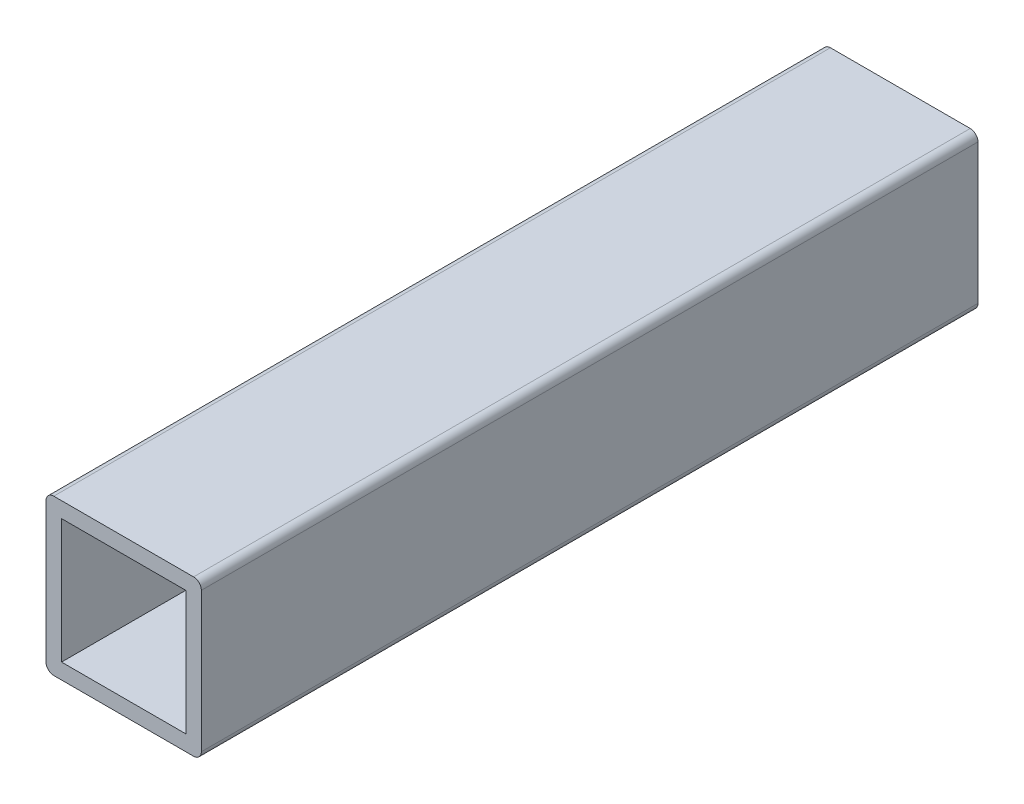
SolidWorks part; units mm, degrees
ref_plane "Front Plane" through (0, 0, 0) normal (0, 0, 1) x (1, 0, 0)
ref_plane "Top Plane" through (0, 0, 0) normal (0, 1, 0) x (1, 0, 0)
ref_plane "Right Plane" through (0, 0, 0) normal (1, 0, 0) x (0, 0, -1)
sketch "Sketch1" plane through (0, 0, 0) normal (0, 0, 1) x (1, 0, 0)
  line L0 (-12.7, -12.7) -> (-12.7, 12.7)
  line L1 (-15.875, -15.875) -> (15.875, -15.875)
  line L2 (-15.875, -15.875) -> (-15.875, 15.875)
  line L3 (-15.875, 15.875) -> (15.875, 15.875)
  line L4 (15.875, -15.875) -> (15.875, 15.875)
  line L5 (-15.875, -15.875) -> (15.875, 15.875) construction
  line L6 (-15.875, 15.875) -> (15.875, -15.875) construction
  line L7 (-12.7, 12.7) -> (12.7, 12.7)
  line L8 (12.7, -12.7) -> (12.7, 12.7)
  line L9 (-12.7, -12.7) -> (12.7, -12.7)
  point P0 (0, 0)
  point P10 (-12.7, -15.875)
  dimension "Outside Width" = 31.75
  dimension "Outside Height" = 31.75
  dimension "Wall Thickness" = 3.175
sketch "Sketch2" plane through (0, 0, 0) normal (1, 0, 0) x (0, 0, -1)
  line L0 (-914.4, 15.875) -> (914.4, 15.875) construction
  point P2 (0, 15.875)
  point P3 (-882.65, 15.875)
  point P5 (882.65, 15.875)
  dimension "Length" = 1828.8
  dimension "D1" = 31.75
  dimension "D2" = 31.75
extrude "Boss-Extrude1" add sketch "Sketch1" along normal up to vertex (914.4 mm away) and the other way up to vertex (914.4 mm away) up to point (0, 15.875, 914.4) other way up to point (0, 15.875, -914.4)
fillet "Fillet1" radius 1.5875 4 edges at (15.875, 15.875, 0) (-15.875, 15.875, 0) (-15.875, -15.875, 0) (15.875, -15.875, 0)
ref_axis "Center Axis 1" through (0, 0, -1005.84) along (0, 0, 1)
sketch "Sketch5" plane through (0, 0, 914.4) normal (0, 0, 1) x (1, 0, 0)
  line L0 (-14.2875, 15.875) -> (14.2875, 15.875)
  line L1 (-12.7, 12.7) -> (12.7, 12.7)
  line L2 (-12.7, 12.7) -> (-12.7, -12.7)
  line L3 (-12.7, -12.7) -> (12.7, -12.7)
  line L4 (12.7, 12.7) -> (12.7, -12.7)
  line L5 (-15.875, 14.2875) -> (-15.875, -14.2875)
  line L6 (15.875, 14.2875) -> (15.875, -14.2875)
  line L7 (-14.2875, -15.875) -> (14.2875, -15.875)
  arc A0 (15.875, -14.2875) -> (14.2875, -15.875) centre (14.2875, -14.2875) cw
  arc A1 (14.2875, 15.875) -> (15.875, 14.2875) centre (14.2875, 14.2875) cw
  arc A2 (-14.2875, 15.875) -> (-15.875, 14.2875) centre (-14.2875, 14.2875) ccw
  arc A3 (-15.875, -14.2875) -> (-14.2875, -15.875) centre (-14.2875, -14.2875) ccw
extrude "Cut-Extrude1" cut sketch "Sketch5" against normal blind 1670.05
equation "\"D1@Fillet1\"=\"Wall Thickness@Sketch1\"/2"
equation "\"D1@Sketch2\"=\"Outside Width@Sketch1\""
equation "\"D2@Sketch2\"=\"D1@Sketch2\""
